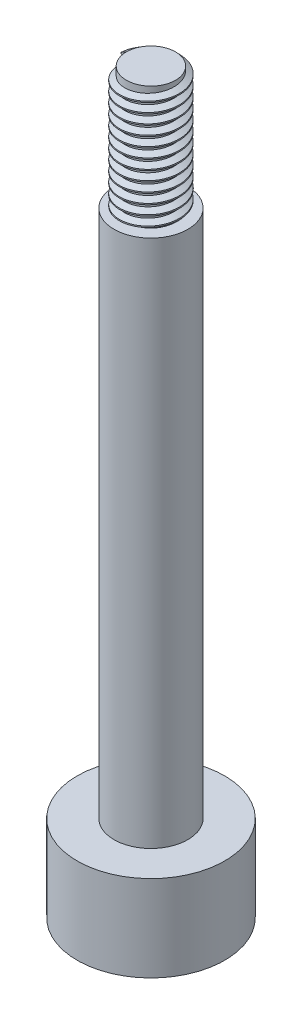
SolidWorks part; units mm, degrees
ref_plane "Plan de face" through (0, 0, 0) normal (0, 0, 1) x (1, 0, 0)
ref_plane "Plan de dessus" through (0, 0, 0) normal (0, 1, 0) x (1, 0, 0)
ref_plane "Plan de droite" through (0, 0, 0) normal (1, 0, 0) x (0, 0, -1)
sketch "Esquisse1" plane through (0, 0, 0) normal (0, 0, 1) x (1, 0, 0)
  line L0 (0, 0) -> (3, 0)
  line L1 (0, 0) -> (3, 0) construction
  line L2 (0, 0) -> (0, 30) construction
  line L3 (0, 30) -> (3, 30) construction
  line L4 (3, 0) -> (3, 30) construction
  line L5 (3, 0) -> (3, 3.5)
  line L6 (3, 3.5) -> (1.5, 3.5)
  line L9 (0, 30) -> (0, 0)
  line L10 (1.5, 3.5) -> (1.5, 25)
  line L11 (1.5, 25) -> (1, 25)
  line L12 (1, 25) -> (1, 30)
  line L13 (0, 30) -> (1, 30)
  dimension "D1" = 3
  dimension "D2" = 30
  dimension "D3" = 3.5
  dimension "D4" = 1.5
  dimension "D5" = 5
  dimension "D6" = 1
revolve "Révolution1" add sketch "Esquisse1" angle 360 about L9
thread "Filetage1" pitch 0.4 method extrude profile "Profil de filetage2" start angle 0, offset 0, length 5, pitch 0.4, diameter 2
ref_plane "Plan2" through (-1, 30, 0) normal (0, 0, 1) x (-1, 0, 0)
sketch "Profil de filetage2" plane through (-1, 30, 0) normal (0, 0, 1) x (-1, 0, 0)
  line L0 (0, 0) -> (0, 0.4) construction
  line L1 (0, 0) -> (0.2165, 0.125)
  line L2 (0.2165, 0.125) -> (0.2165, 0.175)
  line L3 (0.2165, 0.175) -> (0, 0.3)
  line L4 (0.2165, 0.15) -> (0, 0.15) construction
  line L11 (0, 0) -> (0, 0.3)
  point P2 (0, 0)
  dimension "Pitch" = 0.4
  dimension "Profile_Angle" = 60
  dimension "Profile_Land" = 0.05
  dimension "Profile_Height" = 0.2165
sketch "Esquisse9" plane through (0, 0, 0) normal (0, -1, 0) x (1, 0, 0)
  line L0 (0, 0) -> (0, 2.5619) construction
  line L1 (1.299, 0.75) -> (0, 1.5)
  line L2 (0, 1.5) -> (-1.299, 0.75)
  line L3 (-1.299, 0.75) -> (-1.299, -0.75)
  line L4 (-1.299, -0.75) -> (0, -1.5)
  line L5 (0, -1.5) -> (1.299, -0.75)
  line L6 (1.299, -0.75) -> (1.299, 0.75)
  circle A0 centre (0, 0) radius 1.5 construction
  dimension "D1" = 3
extrude "Enlèv. mat.-Extru.1" cut sketch "Esquisse9" against normal blind 2.6
